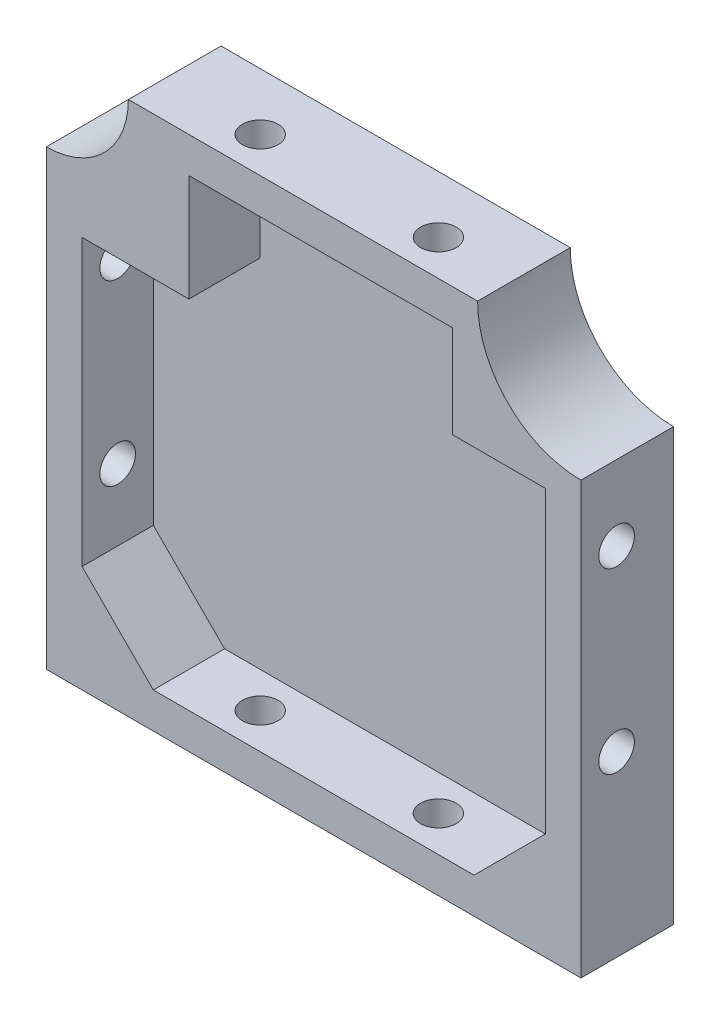
SolidWorks part; units mm, degrees
ref_plane "Plan de face" through (0, 0, 0) normal (0, 0, 1) x (1, 0, 0)
ref_plane "Plan de dessus" through (0, 0, 0) normal (0, 1, 0) x (1, 0, 0)
ref_plane "Plan de droite" through (0, 0, 0) normal (1, 0, 0) x (0, 0, -1)
sketch "Esquisse1" plane through (0, 0, 0) normal (0, 0, 1) x (1, 0, 0)
  line L0 (44.1184, 33.7284) -> (54.1184, 33.7284)
  line L1 (-20.8816, 33.7284) -> (44.1184, 33.7284)
  line L2 (-20.8816, 33.7284) -> (-20.8816, -41.2716)
  line L3 (-20.8816, -41.2716) -> (54.1184, -41.2716)
  line L4 (54.1184, 23.7284) -> (54.1184, -41.2716)
  line L5 (54.1184, 33.7284) -> (54.1184, 23.7284)
  point P6 (54.1184, 33.7284)
  dimension "D1" = 75
  dimension "D2" = 75
extrude "Boss.-Extru.1" add sketch "Esquisse1" along normal blind 13
shell "Coque1" thickness 5 removed face at (16.6184, -3.7716, 13)
sketch "Esquisse2" plane through (-20.8816, 0, 0) normal (-1, 0, 0) x (0, 0, 1)
  line L0 (13, 33.7284) -> (13, -41.2716) construction
  line L1 (13, 33.7284) -> (0, 33.7284) construction
  line L2 (13, -41.2716) -> (0, -41.2716) construction
  circle A0 centre (8, 8.7284) radius 2.5
  circle A1 centre (8, -16.2716) radius 2.5
  dimension "D1" = 5
  dimension "D2" = 5
  dimension "D3" = 5
  dimension "D4" = 5
  dimension "D5" = 25
  dimension "D6" = 25
extrude "Enlèv. mat.-Extru.1" cut sketch "Esquisse2" against normal up to surface (75 mm away) contours A1 | A0 region at (-20.8816, -16.2716, 8) up to face at (54.1184, -3.7716, 6.5)
sketch "Esquisse3" plane through (0, -41.2716, 0) normal (0, -1, 0) x (1, 0, 0)
  line L0 (-20.8816, 13) -> (54.1184, 13) construction
  line L2 (54.1184, 13) -> (54.1184, 0) construction
  line L3 (-20.8816, 13) -> (-20.8816, 0) construction
  circle A0 centre (4.1184, 8) radius 2.5
  circle A1 centre (29.1184, 8) radius 2.5
  dimension "D1" = 5
  dimension "D2" = 5
  dimension "D3" = 5
  dimension "D4" = 5
  dimension "D5" = 25
  dimension "D6" = 25
extrude "Enlèv. mat.-Extru.2" cut sketch "Esquisse3" against normal up to surface (75 mm away) up to face at (16.6184, 33.7284, 6.5)
sketch "Esquisse4" plane through (0, 0, 3) normal (0, 0, 1) x (1, 0, 0)
  line L0 (-15.8816, -26.2716) -> (-5.8816, -36.2716)
  line L3 (-15.8816, 28.7284) -> (-15.8816, -36.2716) construction
  line L4 (-5.8816, -36.2716) -> (-15.8816, -36.2716)
  line L5 (54.1184, 33.7284) -> (36.1184, 33.7284)
  line L6 (49.1184, -36.2716) -> (49.1184, 28.7284) construction
  line L7 (54.1184, 33.7284) -> (54.1184, 15.7284)
  line L8 (54.1184, 15.7284) -> (36.1184, 15.7284)
  line L10 (49.1184, -36.2716) -> (49.1184, -26.2716)
  line L11 (49.1184, -26.2716) -> (39.1184, -36.2716)
  line L12 (-15.8816, -36.2716) -> (49.1184, -36.2716) construction
  line L13 (39.1184, -36.2716) -> (49.1184, -36.2716)
  line L14 (-15.8816, -36.2716) -> (-15.8816, -26.2716)
  line L15 (36.1184, 33.7284) -> (36.1184, 15.7284)
  line L16 (-15.8816, 28.7284) -> (-0.8816, 28.7284)
  line L17 (-15.8816, 28.7284) -> (-15.8816, 13.7284)
  line L18 (-15.8816, 13.7284) -> (-0.8816, 13.7284)
  line L19 (-0.8816, 28.7284) -> (-0.8816, 13.7284)
  dimension "D1" = 10
  dimension "D2" = 10
  dimension "D3" = 18
  dimension "D4" = 18
  dimension "D5" = 10
  dimension "D6" = 10
  dimension "D7" = 15
  dimension "D8" = 15
extrude "Boss.-Extru.2" add sketch "Esquisse4" along normal up to surface (10 mm away) up to face at (16.6184, -3.7716, 13)
sketch "Esquisse5" plane through (0, 0, 13) normal (0, 0, 1) x (1, 0, 0)
  line L0 (54.1184, 33.7284) -> (-20.8816, 33.7284) construction
  line L1 (-20.8816, 33.7284) -> (-20.8816, -41.2716) construction
  circle A0 centre (-20.8816, 33.7284) radius 11.5
  circle A1 centre (54.1184, 33.7284) radius 14.5
  dimension "D1" = 23
  dimension "D2" = 29
extrude "Enlèv. mat.-Extru.3" cut sketch "Esquisse5" against normal up to surface (13 mm away) up to face at (16.6184, -3.7716, 0)
